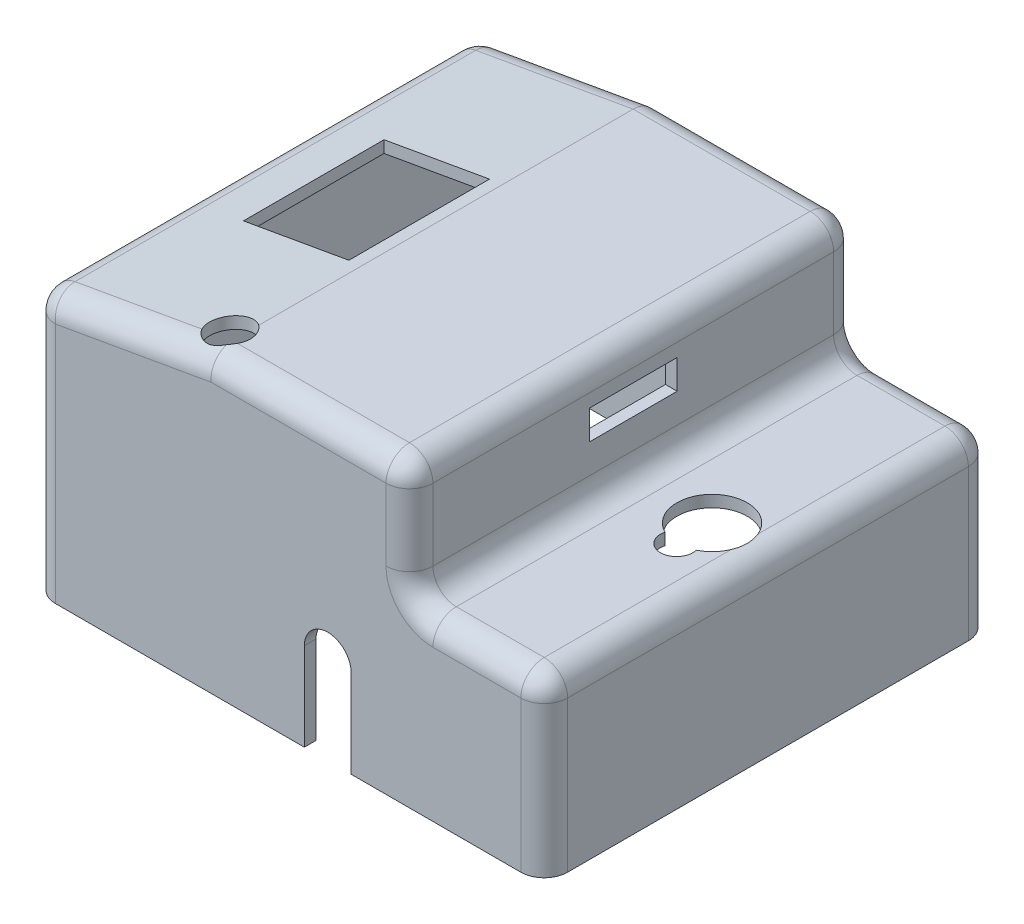
SolidWorks part; units mm, degrees
ref_plane "Přední rovina" through (0, 0, 0) normal (0, 0, 1) x (1, 0, 0)
ref_plane "Horní rovina" through (0, 0, 0) normal (0, 1, 0) x (1, 0, 0)
ref_plane "Pravá rovina" through (0, 0, 0) normal (1, 0, 0) x (0, 0, -1)
sketch "Sketch1" plane through (0, 0, 0) normal (0, 0, 1) x (1, 0, 0)
  line L0 (-41.7, 0) -> (41.7, 0)
  line L4 (-41.7, 0) -> (-41.7, 48)
  line L7 (41.7, 27.75) -> (18.7, 27.75) construction
  line L11 (18.7, 27.75) -> (41.7, 27.75)
  line L12 (41.7, 27.75) -> (41.7, 0)
  line L17 (18.7, 27.75) -> (18.7, 48)
  line L18 (18.7, 48) -> (-41.7, 48)
  dimension "D1" = 83.4
  dimension "D4" = 27.75
  dimension "D5" = 23
  dimension "D9" = 48
extrude "Boss-Extrude1" add sketch "Sketch1" along normal blind 36.2 and the other way blind 36.2
chamfer "Chamfer1" distance 5 angle 80 1 edges at (-41.7, 48, 0) first distance on face at (-41.7, 24, 0)
shell "Shell1" thickness 2 removed face at (0, 0, 0) outward yes
fillet "Fillet2" radius 4 16 edges at (-43.7, 22.3391, -38.2) (-43.7, 22.3391, 38.2) (32.2, 29.75, -38.2) (32.2, 29.75, 38.2) (20.7, 39.875, -38.2) (20.7, 39.875, 38.2) (43.7, 29.75, 0) (20.7, 29.75, 0) (3.5907, 50, -38.2) (20.7, 50, 0) (3.5907, 50, 38.2) (43.7, 14.875, 38.2) (43.7, 14.875, -38.2) (-28.6093, 47.3391, 38.2) (-28.6093, 47.3391, -38.2) (-43.7, 44.6782, 0)
sketch "Sketch2" plane through (0, 0, 0) normal (0, -1, 0) x (1, 0, 0)
  line L0 (41.7, -36.2) -> (35.7, -30.2) construction
  line L1 (41.7, -36.2) -> (35.7, -36.2)
  line L2 (41.7, -36.2) -> (41.7, -30.2)
  line L3 (41.7, -30.2) -> (35.7, -30.2)
  line L4 (35.7, -36.2) -> (35.7, -30.2)
  circle A0 centre (38.7, -33.2) radius 1.45
  dimension "D3" = 2.9
  dimension "D1" = 6
  dimension "D2" = 6
extrude "Boss-Extrude2" add sketch "Sketch2" against normal blind 4 from offset 1.5 offset against normal yes
mirror "Mirror1" about plane through (0, 0, 0) normal (0, 0, 1) of "Boss-Extrude2"
fillet "Fillet3" radius 2 6 edges at (35.7, 3.5, 36.2) (35.7, 3.5, 30.2) (35.7, 3.5, -36.2) (35.7, 3.5, -30.2) (41.7, 3.5, -30.2) (41.7, 3.5, 30.2)
sketch "Sketch3" plane through (0, 29.75, 0) normal (0, 1, 0) x (1, 0, 0)
  line L1 (43.7, 34.2) -> (43.7, -34.2) construction
  circle A0 centre (34.15, 0) radius 6
  circle A1 centre (34.15, -6.05) radius 2.75
  dimension "D1" = 12
  dimension "D2" = 5.5
  dimension "D3" = 6.05
  dimension "D4" = 9.55
extrude "Cut-Extrude1" cut sketch "Sketch3" against normal up to next contours A1 A0 | A0 A1 | A0 A1 | A0 region at (34.15, 29.75, -0.4836) region at (34.15, 29.75, 4.7503) region at (34.15, 29.75, 7.0707)
sketch "Sketch4" plane through (0, 0, 0) normal (0, -1, 0) x (1, 0, 0)
  line L0 (-41.7, -36.2) -> (-41.7, 36.2) construction
  line L1 (-41.7, -10) -> (-36.7, -10)
  line L2 (-41.7, -10) -> (-41.7, 10)
  line L3 (-41.7, 10) -> (-36.7, 10)
  line L4 (-36.7, -10) -> (-36.7, 10)
  line L5 (-41.7, -10) -> (-36.7, 10) construction
  line L6 (-41.7, 10) -> (-36.7, -10) construction
  point P0 (-39.2, 0)
  dimension "D1" = 5
  dimension "D2" = 20
extrude "Boss-Extrude3" add sketch "Sketch4" against normal blind 2 from offset 1.5 offset against normal yes
fillet "Fillet4" radius 2 3 edges at (-41.7, 3.5, 0) (-41.7, 2.5, 10) (-41.7, 2.5, -10)
sketch "Sketch5" plane through (20.7, 0, 0) normal (1, 0, 0) x (0, 0, -1)
  line L1 (-7.5, 43.75) -> (7.5, 43.75)
  line L2 (-7.5, 43.75) -> (-7.5, 38.75)
  line L3 (-7.5, 38.75) -> (7.5, 38.75)
  line L4 (7.5, 43.75) -> (7.5, 38.75)
  line L5 (-7.5, 43.75) -> (7.5, 38.75) construction
  line L6 (-7.5, 38.75) -> (7.5, 43.75) construction
  line L7 (-34.2, 33.75) -> (34.2, 33.75) construction
  point P0 (0, 41.25)
  dimension "D1" = 5
  dimension "D2" = 15
  dimension "D3" = 5
extrude "Cut-Extrude2" cut sketch "Sketch5" against normal up to next
sketch "Sketch6" plane through (0, 0, 38.2) normal (0, 0, 1) x (1, 0, 0)
  line L0 (6.75, 0) -> (6.75, 15) construction
  line L1 (-39.7, 0) -> (39.7, 0) construction
  line L2 (2.75, 0) -> (2.75, 15)
  line L3 (10.75, 0) -> (10.75, 15)
  line L4 (-43.7, 0) -> (-43.7, 41.3218) construction
  arc A0 (2.75, 0) -> (10.75, 0) centre (6.75, 0) ccw
  arc A1 (10.75, 15) -> (2.75, 15) centre (6.75, 15) ccw
  point P4 (6.75, 7.5)
  dimension "D1" = 50.45
  dimension "D2" = 8
  dimension "D3" = 15
extrude "Cut-Extrude3" cut sketch "Sketch6" against normal through all
sketch "Sketch7" plane through (-18.1503, 50, 0) normal (0, 1, 0) x (1, 0, 0)
  line L0 (-25.5497, -34.2) -> (-25.5497, 34.2) construction
  line L1 (2.3085, 12) -> (-15.6915, 12)
  line L2 (2.3085, 12) -> (2.3085, -12)
  line L3 (2.3085, -12) -> (-15.6915, -12)
  line L4 (-15.6915, 12) -> (-15.6915, -12)
  line L5 (2.3085, 12) -> (-15.6915, -12) construction
  line L6 (2.3085, -12) -> (-15.6915, 12) construction
  point P0 (-6.6915, 0)
  dimension "D1" = 18
  dimension "D2" = 24
  dimension "D4" = 18.8582
extrude "Cut-Extrude4" cut sketch "Sketch7" against normal up to next
sketch "Sketch8" plane through (0, 50, 0) normal (0, 1, 0) x (1, 0, 0)
  line L0 (16.7, -38.2) -> (-13.1686, -38.2) construction
  line L2 (-43.7, -34.2) -> (-43.7, 34.2) construction
  circle A0 centre (-15.7, -32.45) radius 3.5
  dimension "D1" = 7
  dimension "D2" = 5.75
  dimension "D3" = 28
extrude "Cut-Extrude5" cut sketch "Sketch8" against normal up to next
